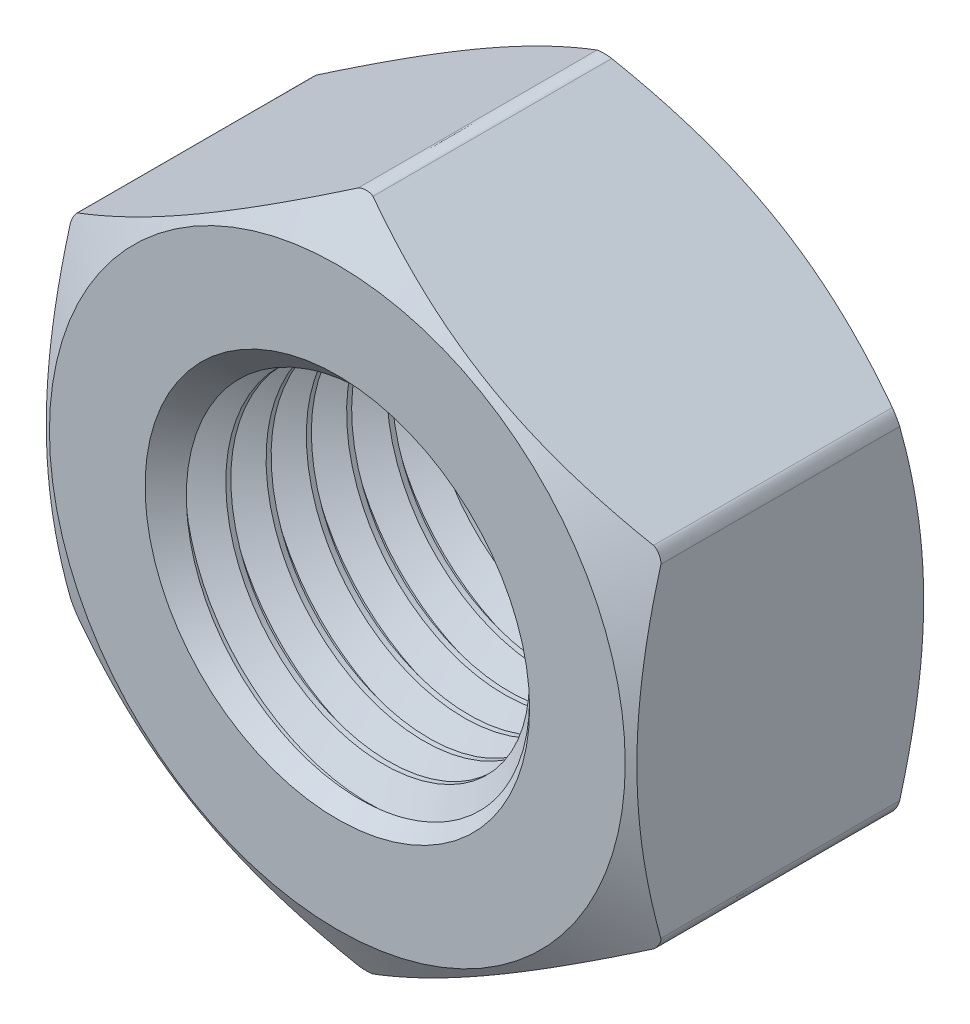
SolidWorks part; units mm, degrees
ref_plane "Front Plane" through (0, 0, 0) normal (0, 0, 1) x (1, 0, 0)
ref_plane "Top Plane" through (0, 0, 0) normal (0, 1, 0) x (1, 0, 0)
ref_plane "Right Plane" through (0, 0, 0) normal (1, 0, 0) x (0, 0, -1)
sketch "Sketch1" plane through (0, 0, 0) normal (0, 0, 1) x (1, 0, 0)
  line L0 (0, -12.7017) -> (0, 12.7017) construction
  line L1 (0, -12.7017) -> (11, -6.3509) construction
  line L2 (11, -6.3509) -> (11, 6.3509) construction
  line L3 (11, 6.3509) -> (0, 12.7017) construction
  line L4 (0, 12.7017) -> (-11, 6.3509) construction
  line L5 (-11, 6.3509) -> (-11, -6.3509) construction
  line L6 (-11, -6.3509) -> (0, -12.7017) construction
  line L7 (-11, 0) -> (11, 0) construction
  line L8 (0, 0) -> (3.5, -6.0622) construction
  circle A0 centre (0, 0) radius 11 construction
  circle A1 centre (0, 0) radius 7 construction
  point P11 (0, 0)
  point P12 (0, -7)
  point P14 (7, 0)
  point P15 (0, 7)
  point P16 (-7, 0)
  point P19 (3.5, -6.0622)
  dimension "Thread Diameter" = 14
  dimension "Width" = 22
  dimension "D1" = 30
sketch "Sketch2" plane through (0, 0, 0) normal (1, 0, 0) x (0, 0, -1)
  line L0 (0, -11) -> (0, 11) construction
  line L1 (-5.5, 11) -> (5.5, 11) construction
  line L2 (-5.5, 11) -> (-5.5, -11) construction
  line L3 (-5.5, -11) -> (5.5, -11) construction
  line L4 (5.5, 11) -> (5.5, -11) construction
  line L5 (5.5, 0) -> (-5.5, 0) construction
  line L8 (-5.5, 7) -> (5.5, 7) construction
  line L9 (-5.5, -7) -> (5.5, -7) construction
  line L10 (-6.9062, 7.1624) -> (-5.4062, 7.1624) construction
  line L11 (-5.4062, 7.1624) -> (-6.1562, 5.8633) construction
  line L12 (-6.1562, 5.8633) -> (-6.9062, 7.1624) construction
  line L13 (-6.8594, 7.0812) -> (-5.4531, 7.0812) construction
  line L14 (-6.8125, 7) -> (-5.5, 7) construction
  line L15 (-6.25, 6.0257) -> (-6.0625, 6.0257) construction
  line L16 (-6.1562, 6.0257) -> (-6.1562, 5.8633) construction
  line L17 (-6.1562, 7.1624) -> (-6.1562, 7) construction
  point P8 (0, 0)
  point P29 (-6.1562, 7.0812)
  dimension "Height" = 11
  dimension "Thread Pitch" = 1.5
  dimension "D2" = 0.1875
sketch "Sketch3" plane through (0, 0, 0) normal (0, 0, 1) x (1, 0, 0)
  line L1 (0, -12.7017) -> (11, -6.3509)
  line L2 (11, -6.3509) -> (11, 6.3509)
  line L3 (11, 6.3509) -> (0, 12.7017)
  line L4 (0, 12.7017) -> (-11, 6.3509)
  line L5 (-11, 6.3509) -> (-11, -6.3509)
  line L6 (-11, -6.3509) -> (0, -12.7017)
  circle A0 centre (0, 0) radius 11 construction
  circle A1 centre (0, 0) radius 6.0257
extrude "Boss-Extrude1" add sketch "Sketch3" along normal up to vertex (5.5 mm away) and the other way up to vertex (5.5 mm away) up to point (0, 0, 5.5) other way up to point (0, 0, -5.5)
sketch "Sketch4" plane through (0, 0, 0) normal (0, 0, 1) x (1, 0, 0)
  circle A0 centre (0, 0) radius 10.725
  dimension "D1" = 21.45
extrude "Cut-Extrude1" cut sketch "Sketch4" against normal through all draft 60 from vertex flip side to cut starting at point (0, 0, 5.5)
extrude "Cut-Extrude2" cut sketch "Sketch4<2>" along normal through all draft 60 from vertex flip side to cut starting at point (0, 0, -5.5)
sketch "Sketch4<2>" plane through (0, 0, 0) normal (0, 0, 1) x (1, 0, 0) same geometry as "Sketch4"
chamfer "Chamfer1" distance 0.9375 angle 45 2 edges at (6.0257, 0, -5.5) (6.0257, 0, 5.5)
fillet "Fillet1" radius 0.55 6 edges at (-11, -6.3509, 0) (-11, 6.3509, 0) (0, -12.7017, 0) (11, -6.3509, 0) (0, 12.7017, 0) (11, 6.3509, 0) conic rho 0.3
ref_axis "Center Axis 1" through (0, 0, -16.7332) along (0, 0, 1)
sketch "Sketch5" plane through (0, 0, 0) normal (0, 0, 1) x (1, 0, 0)
  circle A0 centre (0, 0) radius 7 construction
  circle A1 centre (0, 0) radius 7
extrude "Cut-Extrude3" cut sketch "Sketch5" against normal through all both and the other way through all
sketch "Sketch6" plane through (0, 0, 5.5) normal (0, 0, 1) x (1, 0, 0)
  circle A0 centre (0, 0) radius 7 construction
  circle A1 centre (0, 0) radius 7
curve "Helix/Spiral1" pitch 1.5 height 12.5 radius 7 centre (0, 0, 5.5) axis (0, 0, -1) start towards (0, 1, 0)
sketch "Sketch7" plane through (0, 0, 0) normal (1, 0, 0) x (0, 0, -1)
  line L0 (-6.8594, 7.0812) -> (-5.4531, 7.0812)
  line L1 (-5.4531, 7.0812) -> (-6.0625, 6.0257)
  line L2 (-6.0625, 6.0257) -> (-6.25, 6.0257)
  line L3 (-6.25, 6.0257) -> (-6.8594, 7.0812)
sweep "Sweep1" add profiles "Sketch7" path "Helix/Spiral1"
sketch "Sketch8" plane through (0, 0, 5.5) normal (0, 0, 1) x (1, 0, 0)
  circle A0 centre (0, 0) radius 7.1624
extrude "Cut-Extrude4" cut sketch "Sketch8" against normal through all draft 45 and the other way through all
sketch "Sketch9" plane through (0, 0, -5.5) normal (0, 0, -1) x (-1, 0, 0)
  circle A1 centre (0, 0) radius 7.1624
  circle A2 centre (0, 0) radius 7.1624
  dimension "D1" = 0
extrude "Cut-Extrude5" cut sketch "Sketch9" against normal through all draft 45 and the other way through all
equation "\"D2@Sketch2\" = \"Thread Pitch@Sketch2\" / 8"
equation "\"D1@Chamfer1\"=\"Thread Pitch@Sketch2\"*.625"
equation "\"D1@Sketch4\"=\"Width@Sketch1\"*.975"
equation "\"D1@Fillet1\"=\"Width@Sketch1\"*.025"
equation "\"D4@Helix/Spiral1\"=\"Thread Pitch@Sketch2\""
equation "\"D3@Helix/Spiral1\"=\"Height@Sketch2\"+\"Thread Pitch@Sketch2\""
equation "\"D3@Cut-Extrude2\"=\"D3@Cut-Extrude1\""
